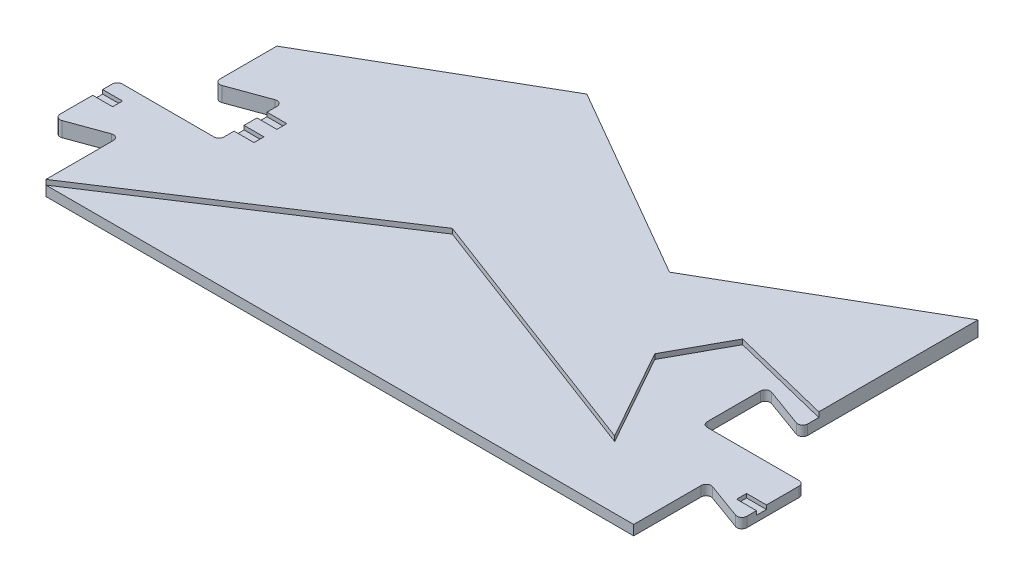
SolidWorks part; units mm, degrees
ref_plane "Přední rovina" through (0, 0, 0) normal (0, 0, 1) x (1, 0, 0)
ref_plane "Horní rovina" through (0, 0, 0) normal (0, 1, 0) x (1, 0, 0)
ref_plane "Pravá rovina" through (0, 0, 0) normal (1, 0, 0) x (0, 0, -1)
sketch "Skica1" plane through (0, 0, 0) normal (0, 1, 0) x (1, 0, 0)
  line L8 (-118.1438, 0) -> (-118.1438, 15)
  line L10 (-118.1438, 15) -> (-128.0938, 11.3785)
  line L11 (-128.0938, 11.3785) -> (-128.0938, 24.2785)
  line L12 (-107.6438, 24.2785) -> (-107.6438, 37.3785)
  line L13 (-107.6438, 37.3785) -> (-118.1432, 33.557)
  line L17 (-118.1432, 33.557) -> (-118.1432, 46.41)
  line L18 (-118.1432, 46.41) -> (-78.6351, 69.22)
  line L19 (-78.6351, 69.22) -> (-39.3176, 46.52)
  line L20 (-118.1438, 15) -> (-118.1438, 56.5658) construction
  line L21 (-107.6438, 24.2785) -> (-128.0938, 24.2785)
  line L22 (-68.7793, 32.3134) -> (-118.1438, 0)
  line L23 (-68.7793, 32.3134) -> (-16.3273, 12.5112)
  line L24 (-16.3273, 12.5112) -> (-26.5931, 30.831)
  line L25 (-26.5931, 30.831) -> (-20.3432, 42.23)
  line L26 (-39.3176, 46.52) -> (0, 69.22)
  line L28 (-118.1438, 0) -> (0, 0)
  line L29 (-20.3432, 42.23) -> (0, 37.22)
  line L30 (0, 0) -> (0, 15)
  line L33 (0, 69.22) -> (0, 0) construction
  line L34 (-10.5, 24.2783) -> (9.9505, 24.2783)
  line L39 (0, 69.22) -> (0, 33.5566)
  line L40 (0, 15) -> (9.9505, 11.3783)
  line L41 (9.9505, 24.2783) -> (9.9505, 11.3783)
  line L42 (0, 33.5566) -> (-10.5, 37.3783)
  line L43 (-10.5, 37.3783) -> (-10.5, 24.2783)
  point P27 (-0.2747, 24.2783)
  dimension "D1" = 45.4
  dimension "D2" = 45.62
  dimension "D3" = 120
  dimension "D4" = 70
  dimension "D5" = 12.9
  dimension "D6" = 13.1
  dimension "D7" = 70
  dimension "D8" = 10.5
  dimension "D9" = 15
  dimension "D10" = 122
  dimension "D11" = 13
  dimension "D12" = 21
  dimension "D13" = 56.0655
  dimension "D14" = 120
  dimension "D15" = 59
  dimension "D16" = 45.4
  dimension "D17" = 120
  dimension "D18" = 118.1438
  dimension "D19" = 104.9
  dimension "D20" = 32.3134
  dimension "D21" = 70
  dimension "D22" = 13.1
  dimension "D23" = 70
  dimension "D24" = 10.5
  dimension "D25" = 15
  dimension "D26" = 12.5112
  dimension "D27" = 69.22
  dimension "D28" = 32
  dimension "D29" = 12.9
  dimension "D30" = 69.22
  dimension "D31" = 9.95
extrude "Přidat vysunutím1" add sketch "Skica1" along normal blind 3 contours L20 L23 L24 L25 L29 L39 L26 L19 L18 L17 L13 L12 L21 | L10 L20 L21 L11 region at (-66.762, 0, -39.2146)
extrude "Přidat vysunutím2" add sketch "Skica1<5>" along normal blind 2 contours L43 L42 L39 L29 L25 L24 L23 L8 L28 L30 L40 L41 L34 region at (-46.7963, 0, -13.9892)
sketch "Skica1<5>" plane through (0, 0, 0) normal (0, 1, 0) x (1, 0, 0) same geometry as "Skica1"
fillet "Zaoblit4" radius 1 12 edges at (0, 1, -33.5566) (-10.5, 1, -24.2783) (-10.5, 1, -37.3783) (0, 1, -15) (9.9505, 1, -11.3783) (9.9505, 1, -24.2783) (-128.0938, 1.5, -11.3785) (-128.0938, 1.5, -24.2785) (-107.6438, 1.5, -24.2785) (-107.6438, 1.5, -37.3785) (-118.1432, 1.5, -33.557) (-118.1438, 1.5, -15)
sketch "Skica2" plane through (0, 3, 0) normal (0, 1, 0) x (1, 0, 0)
  line L1 (-107.6438, 30.6144) -> (-70.1305, 30.6144) construction
  line L3 (-103.6438, 33.9144) -> (-107.6438, 33.9144)
  line L5 (-103.6438, 31.9144) -> (-103.6438, 33.9144)
  line L10 (-128.0938, 18.0426) -> (-90.5805, 18.0426) construction
  line L11 (-128.0938, 12.8066) -> (-128.0938, 23.2785) construction
  line L12 (-68.7793, 32.3134) -> (-118.1438, 0) construction
  line L16 (-124.0938, 21.3426) -> (-128.0938, 21.3426)
  line L17 (-108.6438, 24.2785) -> (-127.0938, 24.2785) construction
  line L18 (-124.0938, 19.3426) -> (-124.0938, 21.3426)
  line L19 (-128.0938, 19.3426) -> (-124.0938, 19.3426)
  line L21 (-107.6438, 31.9144) -> (-103.6438, 31.9144)
  line L22 (-107.6438, 33.9144) -> (-107.6438, 31.9144)
  line L23 (-107.6438, 25.2785) -> (-107.6438, 35.9503) construction
  line L24 (-128.0938, 21.3426) -> (-128.0938, 19.3426)
  line L25 (-103.6438, 29.3144) -> (-103.6438, 27.3144)
  line L26 (-107.6438, 29.3144) -> (-103.6438, 29.3144)
  line L27 (-107.6438, 27.3144) -> (-107.6438, 29.3144)
  line L28 (-103.6438, 27.3144) -> (-107.6438, 27.3144)
  point P6 (-107.6438, 30.6144)
  point P7 (0, 0)
  dimension "D1" = 2
  dimension "D2" = 4
  dimension "D3" = 1.3
  dimension "D4" = 2
  dimension "D5" = 4
  dimension "D6" = 1.3
sketch "Skica3" plane through (0, 2, 0) normal (0, 1, 0) x (1, 0, 0)
  line L0 (9.9505, 18.0424) -> (-19.4268, 18.0424) construction
  line L1 (9.9505, 23.2783) -> (9.9505, 12.8065) construction
  line L2 (-16.3273, 12.5112) -> (-26.5931, 30.831) construction
  line L3 (9.9505, 14.7424) -> (5.9505, 14.7424)
  line L24 (5.9505, 14.7424) -> (5.9505, 16.7424)
  line L25 (5.9505, 16.7424) -> (9.9505, 16.7424)
  line L26 (9.9505, 14.7424) -> (9.9505, 16.7424)
  point P10 (0, 0)
  dimension "D1" = 4
  dimension "D2" = 2
  dimension "D3" = 1.3
extrude "Odebrat vysunutím2" cut sketch "Skica2" against normal blind 0.8
extrude "Odebrat vysunutím3" cut sketch "Skica3" against normal blind 0.8
